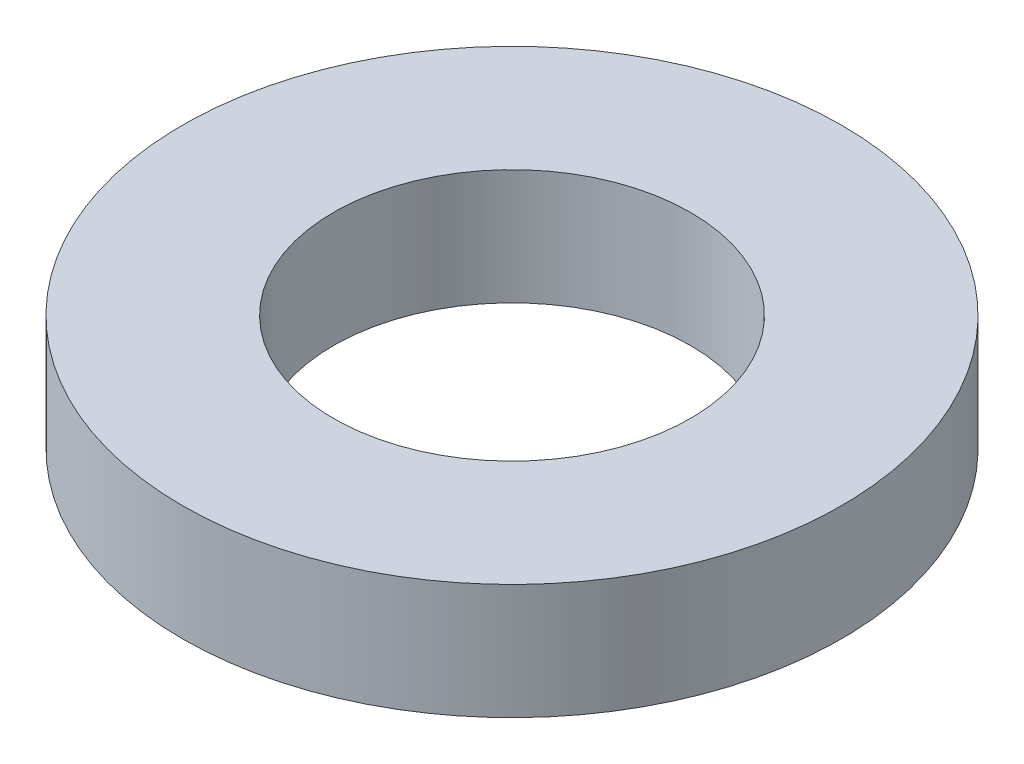
SolidWorks part; units mm, degrees
ref_plane "Front Plane" through (0, 0, 0) normal (0, 0, 1) x (1, 0, 0)
ref_plane "Top Plane" through (0, 0, 0) normal (0, 1, 0) x (1, 0, 0)
ref_plane "Right Plane" through (0, 0, 0) normal (1, 0, 0) x (0, 0, -1)
sketch "Sketch1" plane through (0, 0, 0) normal (0, 1, 0) x (1, 0, 0)
  circle A0 centre (0, 0) radius 60
  dimension "FLANGE_OD" = 120
extrude "Boss-Extrude1" add sketch "Sketch1" along normal blind 21
sketch "Sketch2" plane through (0, 0, 0) normal (0, 1, 0) x (1, 0, 0)
  circle A0 centre (0, 0) radius 32.5
  dimension "BORE_D" = 65
extrude "Cut-Extrude1" cut sketch "Sketch2" along normal through all
sketch "Sketch3" plane through (0, 21, 0) normal (0, 1, 0) x (1, 0, 0)
  circle A0 centre (0, 0) radius 22.8503 construction
  circle A1 centre (-22.8503, 0) radius 4.1663
  dimension "BOLT_D" = 8.3327
  dimension "BOLT_PCD" = 45.7006
extrude "Cut-Extrude2" cut sketch "Sketch3" against normal blind 12.6612 rebuild error yes
pattern_circular "CirPattern1" count 3 over 360 rebuild error yes
